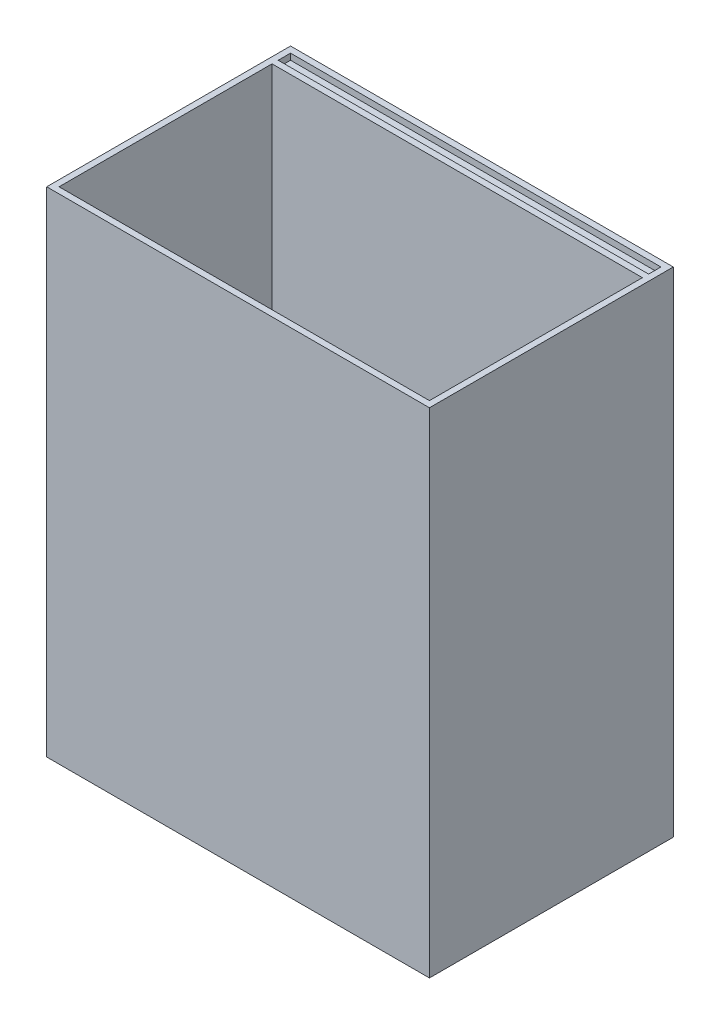
SolidWorks part; units mm, degrees
material "5086-H32, Rod (SS)"
ref_plane "Front Plane" through (0, 0, 0) normal (0, 0, 1) x (1, 0, 0)
ref_plane "Top Plane" through (0, 0, 0) normal (0, 1, 0) x (1, 0, 0)
ref_plane "Right Plane" through (0, 0, 0) normal (1, 0, 0) x (0, 0, -1)
sketch "Sketch1" plane through (0, 0, 0) normal (0, 0, 1) x (1, 0, 0)
  line L1 (0, 0) -> (6200, 0)
  line L2 (0, 0) -> (0, 8000)
  line L3 (0, 8000) -> (6200, 8000)
  line L4 (6200, 0) -> (6200, 8000)
  dimension "D1" = 6200
  dimension "D2" = 8000
extrude "Boss-Extrude1" add sketch "Sketch1" along normal blind 100
sketch "Sketch2" plane through (0, 0, 100) normal (0, 0, 1) x (1, 0, 0)
  line L0 (6200, 0) -> (6200, 8000) construction
  line L1 (0, 0) -> (6200, 0)
  line L2 (0, 0) -> (0, 100)
  line L3 (0, 100) -> (6200, 100)
  line L4 (6200, 0) -> (6200, 100)
  dimension "D1" = 6200
  dimension "D2" = 100
extrude "Boss-Extrude2" add sketch "Sketch2" along normal blind 3850
sketch "Sketch3" plane through (0, 0, 3950) normal (0, 0, 1) x (1, 0, 0)
  line L1 (0, 0) -> (6200, 0)
  line L2 (0, 0) -> (0, 8000)
  line L3 (0, 8000) -> (6200, 8000)
  line L4 (6200, 0) -> (6200, 8000)
  dimension "D1" = 8000
  dimension "D2" = 6200
extrude "Boss-Extrude3" add sketch "Sketch3" against normal blind 100
sketch "Sketch4" plane through (0, 0, 0) normal (0, 0, -1) x (-1, 0, 0)
sketch "Sketch5" plane through (6200, 0, 0) normal (1, 0, 0) x (0, 0, -1)
  line L1 (-3850, 100) -> (-100, 100)
  line L2 (-3850, 100) -> (-3850, 8000)
  line L3 (-3850, 8000) -> (-100, 8000)
  line L4 (-100, 100) -> (-100, 8000)
extrude "Boss-Extrude4" add sketch "Sketch5" against normal blind 100
sketch "Sketch6" plane through (0, 0, 0) normal (-1, 0, 0) x (0, 0, 1)
  line L1 (100, 100) -> (3850, 100)
  line L2 (100, 100) -> (100, 8000)
  line L3 (100, 8000) -> (3850, 8000)
  line L4 (3850, 100) -> (3850, 8000)
extrude "Boss-Extrude5" add sketch "Sketch6" against normal blind 100
sketch "Sketch8" plane through (0, 0, 3850) normal (0, 0, -1) x (-1, 0, 0)
  line L0 (-6100, 8000) -> (-6100, 100) construction
  line L1 (-6100, 1600) -> (0, 1600)
  line L2 (-6100, 1600) -> (-6100, 1401.7231)
  line L3 (-6100, 1401.7231) -> (0, 1401.7231)
  line L4 (0, 1600) -> (0, 1401.7231)
  line L5 (-100, 100) -> (-6100, 100) construction
  dimension "D1" = 1500
extrude "Boss-Extrude7" add sketch "Sketch8" along normal blind 3550
sketch "Sketch9" plane through (0, 1600, 0) normal (0, 1, 0) x (1, 0, 0)
  line L0 (6100, -300) -> (6100, -3850) construction
  line L1 (100, -300) -> (6100, -300)
  line L2 (100, -300) -> (100, -400)
  line L3 (100, -400) -> (6100, -400)
  line L4 (6100, -300) -> (6100, -400)
  dimension "D1" = 100
extrude "Boss-Extrude8" add sketch "Sketch9" along normal blind 6400
sketch "Sketch10" plane through (0, 0, 0) normal (0, -1, 0) x (1, 0, 0)
  line L5 (0, 3950) -> (0, 0) construction
  line L6 (0, 3575) -> (6200, 3575)
  line L7 (0, 3575) -> (0, 3475)
  line L8 (0, 3475) -> (6200, 3475)
  line L9 (6200, 3575) -> (6200, 3475)
  line L10 (6200, 3950) -> (6200, 0) construction
  line L11 (0, 3950) -> (6200, 3950) construction
  line L12 (0, 475) -> (6200, 475)
  line L13 (0, 475) -> (0, 375)
  line L14 (0, 375) -> (6200, 375)
  line L15 (6200, 475) -> (6200, 375)
  line L16 (0, 0) -> (6200, 0) construction
  dimension "D1" = 100
  dimension "D2" = 100
  dimension "D3" = 3000
  dimension "D4" = 475
  dimension "D5" = 475
extrude "Boss-Extrude9" add sketch "Sketch10" against normal blind 1500
sketch "Sketch11" plane through (0, 0, 0) normal (0, 0, -1) x (-1, 0, 0)
  line L0 (-6200, 0) -> (-6200, 8000) construction
  line L1 (-6200, 7900) -> (0, 7900)
  line L2 (-6200, 7900) -> (-6200, 7800)
  line L3 (-6200, 7800) -> (0, 7800)
  line L4 (0, 7900) -> (0, 7800)
  line L5 (0, 8000) -> (0, 0) construction
  line L6 (-6200, 8000) -> (0, 8000) construction
  line L7 (-6200, 5800) -> (0, 5800)
  line L8 (-6200, 5800) -> (-6200, 5700)
  line L9 (-6200, 5700) -> (0, 5700)
  line L10 (0, 5800) -> (0, 5700)
  line L12 (-6200, 5200) -> (0, 5200)
  line L13 (-6200, 5200) -> (-6200, 5100)
  line L14 (-6200, 5100) -> (0, 5100)
  line L15 (0, 5200) -> (0, 5100)
  dimension "D1" = 100
  dimension "D2" = 100
  dimension "D3" = 2000
  dimension "D4" = 100
  dimension "D5" = 100
  dimension "D6" = 500
extrude "Boss-Extrude11" add sketch "Sketch11" against normal blind 300
